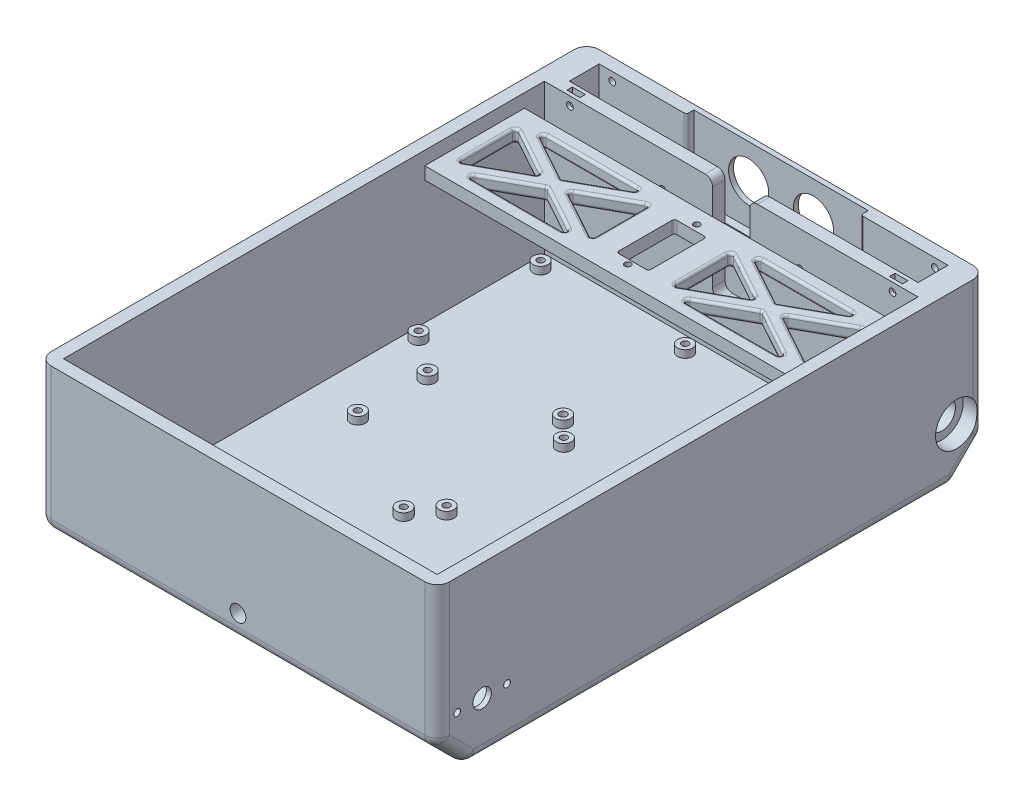
SolidWorks part; units mm, degrees
ref_plane "Front Plane" through (0, 0, 0) normal (0, 0, 1) x (1, 0, 0)
ref_plane "Top Plane" through (0, 0, 0) normal (0, 1, 0) x (1, 0, 0)
ref_plane "Right Plane" through (0, 0, 0) normal (1, 0, 0) x (0, 0, -1)
sketch "Main Body" plane through (0, 0, 0) normal (0, 1, 0) x (1, 0, 0)
  line L0 (-75, 110) -> (75, 110)
  line L1 (-75, -105) -> (75, -105)
  line L2 (-75, -105) -> (-75, 105)
  line L3 (-75, 105) -> (75, 105)
  line L4 (75, -105) -> (75, 105)
  line L5 (-75, -105) -> (75, 105) construction
  line L6 (-75, 105) -> (75, -105) construction
  line L7 (80, -105) -> (80, 105)
  line L8 (-75, -110) -> (75, -110)
  line L9 (-80, -105) -> (-80, 105)
  line L10 (-80, -110) -> (80, -110) construction
  line L11 (-80, -110) -> (-80, 110) construction
  line L12 (80, -110) -> (80, 110) construction
  line L13 (-80, 110) -> (80, 110) construction
  arc A0 (-75, -110) -> (-80, -105) centre (-75, -105) cw
  arc A1 (80, -105) -> (75, -110) centre (75, -105) cw
  arc A2 (75, 110) -> (80, 105) centre (75, 105) cw
  arc A3 (-75, 110) -> (-80, 105) centre (-75, 105) ccw
  point P0 (0, 0)
  dimension "D4" = 5
  dimension "D1" = 75
  dimension "D2" = 210
  dimension "D3" = 5
extrude "Boss-Extrude1" add sketch "Main Body" along normal blind 8 contours L1 L4 L3 L2 | L9 L8 L7 L0 L4 L1 L2 L3 region at (0, 0, -107.2797) region at (0, 0, 0)
extrude "Boss-Extrude3" add sketch "Main Body<4>" along normal blind 60 from surface starting at face at (0, 8, 0)
sketch "Main Body<4>" plane through (0, 0, 0) normal (0, 1, 0) x (1, 0, 0) same geometry as "Main Body"
sketch "Sketch1" plane through (75, 0, 0) normal (-1, 0, 0) x (0, 0, 1)
  line L0 (105, 68) -> (105, 8) construction
  line L1 (-105, 8) -> (105, 8) construction
  line L2 (79, 15.5) -> (105, 15.5)
  line L3 (79, 8) -> (105, 8)
  line L4 (79, 8) -> (79, 34)
  line L5 (79, 34) -> (105, 34)
  line L6 (105, 8) -> (105, 34)
  line L7 (79, 8) -> (105, 34) construction
  line L8 (79, 34) -> (105, 8) construction
  circle A0 centre (92, 21) radius 13
  line M2 (-105, 8) -> (105, 8)
  line M3 (105, 8) -> (105, 68)
  dimension "D1" = 26
  dimension "D2" = 7.5
extrude "Boss-Extrude4" add sketch "Sketch1" along normal up to surface (150 mm away) contours A0 L4 M2 | A0 L3 M3 region at (75, 10.5201, 82.0674) region at (75, 10.5201, 101.9326) up to face at (-75, 38, 0)
sketch "Sketch2" plane through (0, 0, 0) normal (1, 0, 0) x (0, 0, -1)
  line L0 (-105, 68) -> (-105, 15.5) construction
  line L1 (-105, 8) -> (-79, 8)
  line L2 (-105, 8) -> (-105, 15.5)
  line L3 (-105, 15.5) -> (-79, 15.5)
  line L4 (-79, 8) -> (-79, 15.5)
  line L5 (105, 8) -> (-79, 8) construction
  line L6 (-79, 8) -> (-79, 15.5) construction
  line L7 (-79, 15.5) -> (-80.2208, 15.5) construction
extrude "Cut-Extrude1" cut sketch "Sketch2" against normal mid plane 12
sketch "Sketch3" plane through (0, 8, 0) normal (0, 1, 0) x (1, 0, 0)
  line L0 (75, -105) -> (-75, -105) construction
  line L1 (-4, -79) -> (-11, -79)
  line L2 (-4, -79) -> (-4, -105)
  line L3 (-4, -105) -> (-11, -105)
  line L4 (-11, -79) -> (-11, -105)
  line L5 (0, 0) -> (0, -105) construction
  line L6 (-75, -79) -> (-6, -79) construction
  line L7 (11, -79) -> (11, -105)
  line L8 (4, -105) -> (11, -105)
  line L9 (4, -79) -> (4, -105)
  line L10 (4, -79) -> (11, -79)
  line L11 (-6, -103.7792) -> (-6, -92) construction
  dimension "D1" = 5
  dimension "D2" = 4
extrude "Boss-Extrude5" add sketch "Sketch3" along normal blind 20
sketch "Sketch4" plane through (0, 8, 0) normal (0, 1, 0) x (1, 0, 0)
  line L0 (-75, -105) -> (-75, 105) construction
  line L1 (-75, 93) -> (75, 93)
  line L2 (-75, 93) -> (-75, 88)
  line L3 (-75, 88) -> (75, 88)
  line L4 (75, 93) -> (75, 88)
  line L5 (75, 105) -> (75, -105) construction
  line L6 (-75, 105) -> (75, 105) construction
  dimension "D1" = 17
  dimension "D2" = 5
extrude "Boss-Extrude6" add sketch "Sketch4" along normal up to surface (60 mm away) up to face at (0, 68, 0)
sketch "Sketch5" plane through (80, 0, 0) normal (1, 0, 0) x (0, 0, -1)
  circle A0 centre (-92, 21) radius 3.5 construction
  circle A1 centre (-92, 21) radius 3.5
  circle A2 centre (-92, 21) radius 3.7
  dimension "D1" = 0.2
extrude "Cut-Extrude4" cut sketch "Sketch5" against normal up to next contours A1 | A2 A1 region at (80, 21, 92) region at (80, 21, 95.5953)
sketch "Sketch6" plane through (-75, 0, 0) normal (1, 0, 0) x (0, 0, -1)
  circle A0 centre (-92, 21) radius 13
  dimension "D1" = 26
extrude "Cut-Extrude5" cut sketch "Sketch6" against normal offset from surface (3 mm away) 2 up to face at (-80, 34, 0)
mirror "Mirror1" about plane through (0, 0, 0) normal (1, 0, 0) of "Cut-Extrude4"
sketch "Sketch8" plane through (75, 0, 0) normal (-1, 0, 0) x (0, 0, 1)
  circle A0 centre (92, 21) radius 13
  dimension "D1" = 26
extrude "Cut-Extrude6" cut sketch "Sketch8" against normal offset from surface (3 mm away) 2 up to face at (80, 21, 88.3)
sketch "Sketch10" plane through (80, 0, 0) normal (1, 0, 0) x (0, 0, -1)
  circle A1 centre (-82, 21) radius 1.25
  circle A2 centre (-82, 21) radius 1.25
  circle A3 centre (-102, 21) radius 1.25
  circle A4 centre (-102, 21) radius 1.25
  circle A5 centre (-92, 21) radius 12.5
  circle A6 centre (-92, 21) radius 12.5
  circle A63 centre (-102, 21) radius 1.35
  circle A64 centre (-82, 21) radius 1.35
  dimension "D4" = 2.7
extrude "Cut-Extrude7" cut sketch "Sketch10" against normal up to next contours A2 | A64 A2 | A4 | A63 A4 region at (80, 21, 82) region at (80, 21, 102) region at (80, 21, 103.3118) region at (80, 21, 83.3118)
mirror "Mirror3" about plane through (0, 0, 0) normal (1, 0, 0) of "Cut-Extrude7"
sketch "Sketch11" plane through (80, 0, 0) normal (1, 0, 0) x (0, 0, -1)
  circle A0 centre (98.55, 21.05) radius 4.45 construction
  circle A1 centre (98.55, 21.05) radius 4.45
  circle A3 centre (98.55, 21.05) radius 5.45
  dimension "D1" = 1
extrude "Cut-Extrude10" cut sketch "Sketch11" against normal through all contours A1 | A3 A1 region at (80, 21.05, -98.55) region at (80, 21.05, -93.2541)
sketch "Sketch12" plane through (-75, 0, 0) normal (1, 0, 0) x (0, 0, -1)
  line L0 (93, 8) -> (105, 8) construction
  line L1 (93, 68) -> (105, 68)
  line L2 (93, 68) -> (93, 8)
  line L3 (93, 8) -> (105, 8)
  line L4 (105, 68) -> (105, 8)
  line L6 (93, 68) -> (93, 8) construction
  line L7 (93, 68) -> (105, 68) construction
  circle A2 centre (98.55, 21.05) radius 5.45 construction
  circle A3 centre (98.55, 21.05) radius 5.45
extrude "Boss-Extrude7" add sketch "Sketch12" along normal blind 5
sketch "Sketch13" plane through (-80, 0, 0) normal (-1, 0, 0) x (0, 0, 1)
  circle A0 centre (-98.55, 21.05) radius 8.55
  circle A2 centre (-98.55, 21.05) radius 5.45 construction
  dimension "D1" = 17.1
extrude "Cut-Extrude11" cut sketch "Sketch13" against normal blind 6
mirror "Mirror4" about plane through (0, 0, 0) normal (1, 0, 0) of "Boss-Extrude7", "Cut-Extrude11"
sketch "Sketch14" plane through (0, 8, 0) normal (0, 1, 0) x (1, 0, 0)
  line L0 (-4, -105) -> (-4, -79) construction
  line L1 (-4, -95) -> (4, -95)
  line L2 (-4, -95) -> (-4, -105)
  line L3 (-4, -105) -> (4, -105)
  line L4 (4, -95) -> (4, -105)
  dimension "D1" = 10
extrude "Boss-Extrude9" add sketch "Sketch14" along normal blind 5
sketch "Sketch15" plane through (0, 0, 110) normal (0, 0, 1) x (1, 0, 0)
  arc A4 (3.15, 19.5) -> (-3.15, 19.5) centre (0, 19.5) ccw
  arc A5 (-3.15, 19.5) -> (3.15, 19.5) centre (0, 19.5) ccw
  arc A6 (3, 19.5) -> (-3, 19.5) centre (0, 19.5) ccw construction
  point P0 (3.8067, 18.2485)
  dimension "D1" = 3.15
extrude "Cut-Extrude12" cut sketch "Sketch15" against normal up to next contours A4 A5 region at (0, 19.5, 110)
sketch "Sketch16" plane through (0, 0, 0) normal (0, -1, 0) x (1, 0, 0)
  circle A0 centre (-12.5, -82) radius 1.475 construction
  circle A1 centre (-70.5, -82) radius 1.475 construction
  circle A2 centre (-70.5, -33) radius 1.475 construction
  circle A3 centre (-12.5, -33) radius 1.475 construction
  circle A4 centre (-4.2, -25) radius 1.475 construction
  circle A5 centre (-55, -21.12) radius 1.475 construction
  circle A6 centre (-55, 6.88) radius 1.475 construction
  circle A7 centre (-4.2, 22.08) radius 1.475 construction
  circle A8 centre (-12.3, 31.18) radius 1.475 construction
  circle A9 centre (24.2, 31.18) radius 1.475 construction
  circle A10 centre (37.8459, 24.117) radius 1.475 construction
  circle A11 centre (59.5541, 24.117) radius 1.475 construction
  circle A12 centre (59.5541, 68.243) radius 1.475 construction
  circle A13 centre (37.8459, 68.243) radius 1.475 construction
  circle A14 centre (24.2, 67.68) radius 1.475 construction
  circle A15 centre (-12.3, 67.68) radius 1.475 construction
  circle A16 centre (-12.5, -82) radius 1.475
  circle A17 centre (-70.5, -82) radius 1.475
  circle A18 centre (-70.5, -33) radius 1.475
  circle A19 centre (-12.5, -33) radius 1.475
  circle A20 centre (-4.2, -25) radius 1.475
  circle A21 centre (-55, -21.12) radius 1.475
  circle A22 centre (-55, 6.88) radius 1.475
  circle A23 centre (-4.2, 22.08) radius 1.475
  circle A24 centre (-12.3, 31.18) radius 1.475
  circle A25 centre (24.2, 31.18) radius 1.475
  circle A26 centre (37.8459, 24.117) radius 1.475
  circle A27 centre (59.5541, 24.117) radius 1.475
  circle A28 centre (59.5541, 68.243) radius 1.475
  circle A29 centre (37.8459, 68.243) radius 1.475
  circle A30 centre (24.2, 67.68) radius 1.475
  circle A31 centre (-12.3, 67.68) radius 1.475
  circle A32 centre (-70.5, -82) radius 1.35
  circle A33 centre (-12.5, -82) radius 1.35
  circle A34 centre (-12.5, -33) radius 1.35
  circle A35 centre (-4.2, -25) radius 1.35
  circle A36 centre (-55, -21.12) radius 1.35
  circle A37 centre (-70.5, -33) radius 1.35
  circle A38 centre (-55, 6.88) radius 1.35
  circle A39 centre (-12.3, 31.18) radius 1.35
  circle A40 centre (-4.2, 22.08) radius 1.35
  circle A41 centre (24.2, 31.18) radius 1.35
  circle A42 centre (37.8459, 24.117) radius 1.35
  circle A43 centre (59.5541, 24.117) radius 1.35
  circle A44 centre (37.8459, 68.243) radius 1.35
  circle A45 centre (59.5541, 68.243) radius 1.35
  circle A46 centre (24.2, 67.68) radius 1.35
  circle A47 centre (-12.3, 67.68) radius 1.35
  dimension "D1" = 2.7
extrude "Cut-Extrude13" cut sketch "Sketch16" against normal up to next contours A47 | A46 | A44 | A45 | A35 | A37 | A36 | A38 | A39 | A40 | A41 | A42 | A43 | A32 | A33 | A19 region at (-70.5, 0, -82) region at (-12.5, 0, -82) region at (-4.2, 0, -25) region at (-55, 0, -21.12) region at (-70.5, 0, -33) region at (-55, 0, 6.88) region at (-12.3, 0, 31.18) region at (-4.2, 0, 22.08) region at (24.2, 0, 31.18) region at (37.8459, 0, 24.117) region at (59.5541, 0, 24.117) region at (37.8459, 0, 68.243) region at (59.5541, 0, 68.243) region at (24.2, 0, 67.68) region at (-12.3, 0, 67.68)
sketch "Sketch18" plane through (75, 0, 0) normal (-1, 0, 0) x (0, 0, 1)
  line L1 (-80, 62.6) -> (-40, 62.6)
  line L2 (-80, 62.6) -> (-80, 57.6)
  line L3 (-80, 57.6) -> (-40, 57.6)
  line L4 (-40, 62.6) -> (-40, 57.6)
  line L5 (-88, 68) -> (105, 68) construction
  dimension "D1" = 5
  dimension "D2" = 30
  dimension "D3" = 40
  dimension "D4" = 5.4
extrude "Boss-Extrude11" add sketch "Sketch18" along normal up to next
sketch "Sketch19" plane through (0, 68, 0) normal (0, 1, 0) x (1, 0, 0)
  line L1 (-6.425, 71.625) -> (6.425, 71.625)
  line L2 (-6.425, 71.625) -> (-6.425, 48.375)
  line L3 (-6.425, 48.375) -> (6.425, 48.375)
  line L4 (6.425, 71.625) -> (6.425, 48.375)
  line L12 (-75, 80) -> (-75, 40)
  line L13 (-75, 40) -> (75, 40)
  line L14 (75, 40) -> (75, 80)
  line L15 (75, 80) -> (-75, 80)
  line L16 (-75, 80) -> (-75, 40)
  line L17 (-75, 40) -> (75, 40)
  line L18 (75, 40) -> (75, 80)
  line L19 (75, 80) -> (-75, 80)
  point P4 (0, 71.625)
  point P8 (0, 80)
  point P12 (6.425, 60)
  point P13 (75, 60)
  dimension "D1" = 23.25
  dimension "D2" = 12.85
  dimension "D3" = 0
extrude "Cut-Extrude14" cut sketch "Sketch19" against normal up to next contours L4 L1 L2 L3 region at (0, 68, -60)
sketch "Sketch21" plane through (0, 0, -110) normal (0, 0, -1) x (-1, 0, 0)
  circle A1 centre (-64.75, 64.5) radius 1.3
  circle A2 centre (-64.75, 64.5) radius 1.3
  circle A3 centre (64.75, 64.5) radius 1.3
  circle A4 centre (64.75, 64.5) radius 1.3
  circle A44 centre (-64.75, 64.5) radius 1.35
  circle A45 centre (64.75, 64.5) radius 1.35
  dimension "D3" = 2.7
extrude "Cut-Extrude16" cut sketch "Sketch21" against normal up to surface (22 mm away) contours A44 A2 | A2 | A45 A4 | A4 region at (64.75, 64.5, -110) region at (-64.75, 64.5, -110) region at (66.0618, 64.5, -110) region at (-63.4382, 64.5, -110) up to face at (0, 38, -88)
ref_plane "Plane1" through (0, 0, -90.5) normal (0, 0, -1) x (-1, 0, 0)
sketch "Sketch22" plane through (0, 0, -90.5) normal (0, 0, -1) x (-1, 0, 0)
  line L0 (-67.35, 66.0011) -> (-67.35, 68)
  line L1 (-62.15, 66.0011) -> (-64.75, 67.5022)
  line L2 (-64.75, 67.5022) -> (-67.35, 66.0011)
  line L3 (-67.35, 66.0011) -> (-67.35, 62.9989)
  line L4 (-67.35, 62.9989) -> (-64.75, 61.4978)
  line L5 (-64.75, 61.4978) -> (-62.15, 62.9989)
  line L6 (-62.15, 62.9989) -> (-62.15, 66.0011)
  line L7 (-67.35, 68) -> (-62.15, 68)
  line L8 (-62.15, 68) -> (-62.15, 66.0011)
  line L9 (70, 68) -> (-70, 68) construction
  line L10 (0, 0) -> (0, 68) construction
  line L11 (75, 68) -> (-75, 68) construction
  line L12 (64.75, 61.4978) -> (62.15, 62.9989)
  line L13 (67.35, 62.9989) -> (64.75, 61.4978)
  line L14 (64.75, 67.5022) -> (67.35, 66.0011)
  line L15 (67.35, 66.0011) -> (67.35, 62.9989)
  line L16 (67.35, 66.0011) -> (67.35, 68)
  line L17 (62.15, 62.9989) -> (62.15, 66.0011)
  line L18 (62.15, 68) -> (62.15, 66.0011)
  line L19 (67.35, 68) -> (62.15, 68)
  line L20 (62.15, 66.0011) -> (64.75, 67.5022)
  circle A0 centre (-64.75, 64.5) radius 2.6 construction
  circle A1 centre (-64.75, 64.5) radius 1.35 construction
  dimension "D1" = 5.2
extrude "Cut-Extrude17" cut sketch "Sketch22" against normal mid plane 2.2 contours L20 L17 L12 L13 L15 L14 | L18 L20 L14 L16 L19 | L5 L6 L1 L2 L3 L4 | L8 L7 L0 L2 L1 region at (67.2943, 67.0006, -90.5) region at (64.75, 64.5, -90.5) region at (-64.75, 64.5, -90.5) region at (-62.2057, 67.0006, -90.5)
sketch "Sketch23" plane through (0, 0, -110) normal (0, 0, -1) x (-1, 0, 0)
  circle A0 centre (64.75, 64.5) radius 2.5
  circle A1 centre (-64.75, 64.5) radius 2.5
  circle A2 centre (64.75, 64.5) radius 1.35 construction
  circle A3 centre (-64.75, 64.5) radius 1.35 construction
  dimension "D1" = 5
  dimension "D2" = 5
extrude "Cut-Extrude18" cut sketch "Sketch23" against normal mid plane 2.5
sketch "Sketch24" plane through (0, 62.6, 0) normal (0, 1, 0) x (1, 0, 0)
  circle A0 centre (0, 46.475) radius 1.2502
  arc A1 (0.4, 45.5583) -> (-0.4, 45.5583) centre (0, 46.475) ccw construction
  circle A2 centre (0, 74.175) radius 1.2502
  arc A3 (-0.4, 75.0917) -> (0, 73.1748) centre (0, 74.175) ccw construction
  point P5 (0.4, 45.5583)
  dimension "D1" = 0.25
extrude "Cut-Extrude19" cut sketch "Sketch24" against normal up to next
sketch "Sketch25" plane through (0, 62.6, 0) normal (0, 1, 0) x (1, 0, 0)
  line L1 (-11.3, 80) -> (11.3, 80)
  line L2 (-11.3, 80) -> (-11.3, 40)
  line L3 (-11.3, 40) -> (11.3, 40)
  line L4 (-75, 80) -> (-75, 40)
  line L5 (-75, 40) -> (75, 40)
  line L6 (75, 40) -> (75, 80)
  line L7 (75, 80) -> (-75, 80)
  line L8 (-75, 80) -> (-75, 40)
  line L9 (-75, 40) -> (75, 40)
  line L10 (75, 40) -> (75, 80)
  line L11 (75, 80) -> (-75, 80)
  line L12 (11.3, 80) -> (11.3, 40)
  line L13 (-11.3, 80) -> (11.3, 40) construction
  line L14 (-11.3, 40) -> (11.3, 80) construction
  line L15 (0, 80) -> (0, 40) construction
  line L16 (70, 75) -> (70, 45)
  line L17 (-70, 75) -> (-16.3, 75)
  line L18 (-70, 75) -> (-70, 45)
  line L19 (-70, 45) -> (-16.3, 45)
  line L20 (-16.3, 75) -> (-16.3, 45)
  line L21 (-70, 75) -> (-16.3, 45) construction
  line L22 (-70, 45) -> (-16.3, 75) construction
  line L23 (70, 75) -> (16.3, 45) construction
  line L24 (70, 45) -> (16.3, 75) construction
  line L25 (70, 75) -> (16.3, 75)
  line L26 (16.3, 75) -> (16.3, 45)
  line L27 (70, 45) -> (16.3, 45)
  line L28 (-75, 60) -> (-11.3, 60) construction
  line L29 (75, 60) -> (11.3, 60) construction
  line L30 (-70, 71.9362) -> (-48.3314, 60)
  line L31 (-16.3, 71.9362) -> (-37.9686, 60)
  line L32 (70, 71.9362) -> (48.3314, 60)
  line L33 (-48.3314, 60) -> (-70, 48.0638)
  line L34 (48.3314, 60) -> (70, 48.0638)
  line L35 (-65.199, 45) -> (-43.15, 57.1458)
  line L36 (65.199, 45) -> (43.15, 57.1458)
  line L37 (-43.15, 57.1458) -> (-21.101, 45)
  line L38 (43.15, 57.1458) -> (21.101, 45)
  line L39 (16.3, 71.9362) -> (37.9686, 60)
  line L40 (-37.9686, 60) -> (-16.3, 48.0638)
  line L41 (37.9686, 60) -> (16.3, 48.0638)
  line L42 (-65.199, 75) -> (-43.15, 62.8542)
  line L43 (65.199, 75) -> (43.15, 62.8542)
  line L44 (-43.15, 62.8542) -> (-21.101, 75)
  line L45 (43.15, 62.8542) -> (21.101, 75)
  line L46 (-75, 40) -> (-75, 80) construction
  line L47 (-75, 40) -> (75, 40) construction
  point P2 (0, 60)
  point P9 (-43.15, 60)
  point P10 (75, 60)
  point P24 (43.15, 60)
  point P62 (-54.1745, 68.9271)
  dimension "D2" = 150
  dimension "D3" = 5
  dimension "D4" = 5
  dimension "D5" = 5
  dimension "D6" = 26.6686
  dimension "D7" = 96.101
  dimension "D1" = 0
extrude "Cut-Extrude21" cut sketch "Sketch25" against normal up to next contours L37 L35 L19 | L33 L30 L18 | L42 L44 L17 | L31 L40 L20 | L41 L39 L26 | L45 L43 L25 | L36 L38 L27 | L32 L34 L16 region at (62.7771, 62.6, -60) region at (43.15, 62.6, -70.9514) region at (43.15, 62.6, -49.0486) region at (23.5229, 62.6, -60) region at (-43.15, 62.6, -70.9514) region at (-62.7771, 62.6, -60) region at (-23.5229, 62.6, -60) region at (-43.15, 62.6, -49.0486)
sketch "Sketch26" plane through (-80, 0, 0) normal (-1, 0, 0) x (0, 0, 1)
  line L0 (-110, 12.58) -> (-97.42, 0)
  line L1 (-110, 68) -> (-110, 0) construction
  line L2 (105, 0) -> (-105, 0) construction
  line L3 (-97.42, 0) -> (-92.42, 0)
  line L4 (-92.42, 0) -> (-110, 17.58)
  line L5 (-110, 17.58) -> (-110, 12.58)
  line L6 (-110, 12.58) -> (-110, 0)
  line L7 (-110, 0) -> (-97.42, 0)
  circle A1 centre (-98.55, 21.05) radius 8.55 construction
  line M5 (-105, 15.4375) -> (-105, 0)
  line M6 (-105, 0) -> (105, 0)
  dimension "D1" = 2
  dimension "D2" = 5
  dimension "D3" = 45
extrude "Cut-Extrude22" cut sketch "Sketch26" against normal up to next contours L6 L7 L0 M5 | L0 M5 M6 region at (-80, 5.1434, -107.7067) region at (-80, 2.5267, -102.4733)
mirror "Mirror5" about plane through (0, 0, 0) normal (0, 0, 1) of "Cut-Extrude22"
fillet "Fillet1" radius 5 14 edges at (80, 3.79, -101.21) (78.5355, 11.1156, -108.5355) (-80, 3.79, -101.21) (-78.5355, 11.1156, -108.5355) (80, 3.79, 101.21) (78.5355, 11.1156, 108.5355) (-80, 3.79, 101.21) (-78.5355, 11.1156, 108.5355) (0, 0, -97.42) (0, 12.58, -110) (0, 0, 97.42) (0, 12.58, 110) (-80, 0, 0) (80, 0, 0)
fillet "Fillet2" radius 1 76 edges at (-32.1255, 57.6, -51.0729) (-32.1255, 62.6, -51.0729) (-21.101, 60.1, -45) (-43.15, 62.6, -45) (-43.15, 57.6, -45) (-54.1745, 57.6, -51.0729) (-65.199, 60.1, -45) (-54.1745, 62.6, -51.0729) (-43.15, 60.1, -57.1458) (32.1255, 57.6, -68.9271) (32.1255, 62.6, -68.9271) (21.101, 60.1, -75) (43.15, 62.6, -75) (43.15, 57.6, -75) (54.1745, 57.6, -68.9271) (65.199, 60.1, -75) (54.1745, 62.6, -68.9271) (43.15, 60.1, -62.8542) (54.1745, 62.6, -51.0729) (54.1745, 57.6, -51.0729) (43.15, 57.6, -45) (65.199, 60.1, -45) (43.15, 62.6, -45) (21.101, 60.1, -45) (32.1255, 62.6, -51.0729) (43.15, 60.1, -57.1458) (32.1255, 57.6, -51.0729) (59.1657, 62.6, -65.9681) (59.1657, 57.6, -65.9681) (70, 57.6, -60) (70, 60.1, -71.9362) (70, 62.6, -60) (70, 60.1, -48.0638) (59.1657, 62.6, -54.0319) (48.3314, 60.1, -60) (59.1657, 57.6, -54.0319) (-54.1745, 62.6, -68.9271) (-54.1745, 57.6, -68.9271) (-43.15, 57.6, -75) (-65.199, 60.1, -75) (-43.15, 62.6, -75) (-21.101, 60.1, -75) (-32.1255, 62.6, -68.9271) (-43.15, 60.1, -62.8542) (-32.1255, 57.6, -68.9271) (-59.1657, 57.6, -54.0319) (-59.1657, 62.6, -54.0319) (-70, 60.1, -48.0638) (-70, 62.6, -60) (-70, 57.6, -60) (-59.1657, 57.6, -65.9681) (-70, 60.1, -71.9362) (-59.1657, 62.6, -65.9681) (-48.3314, 60.1, -60) (-27.1343, 62.6, -65.9681) (-27.1343, 57.6, -65.9681) (-16.3, 57.6, -60) (-16.3, 60.1, -71.9362) (-16.3, 62.6, -60) (-16.3, 60.1, -48.0638) (-27.1343, 62.6, -54.0319) (-37.9686, 60.1, -60) (-27.1343, 57.6, -54.0319) (27.1343, 57.6, -54.0319) (27.1343, 62.6, -54.0319) (16.3, 60.1, -48.0638) (16.3, 62.6, -60) (16.3, 57.6, -60) (27.1343, 57.6, -65.9681) (16.3, 60.1, -71.9362) (27.1343, 62.6, -65.9681) (37.9686, 60.1, -60) (6.425, 60.1, -48.375) (-6.425, 60.1, -48.375) (-6.425, 60.1, -71.625) (6.425, 60.1, -71.625)
sketch "Sketch33" plane through (0, 0, -110) normal (0, 0, -1) x (-1, 0, 0)
  circle A0 centre (-13, 53.9999) radius 8.075
  circle A1 centre (13, 53.9999) radius 8.075
  circle A2 centre (-13, 53.9999) radius 7.3 construction
  circle A3 centre (13, 53.9999) radius 7.3 construction
  dimension "D1" = 16.15
extrude "Cut-Extrude27" cut sketch "Sketch33" against normal up to next
sketch "Sketch34" plane through (0, 0, -93) normal (0, 0, -1) x (-1, 0, 0)
  circle A0 centre (27.525, 54) radius 1.35 construction
  circle A1 centre (27.525, 54) radius 1.35
  circle A2 centre (-27.525, 54) radius 1.35 construction
  circle A3 centre (-27.525, 54) radius 1.35
  circle A4 centre (-27.525, 54) radius 1.35
  circle A5 centre (27.525, 54) radius 1.35
  dimension "D1" = 2.7
  dimension "D2" = 2.7
extrude "Cut-Extrude28" cut sketch "Sketch34" against normal up to next contours A3 | A1 region at (-27.525, 54, -93) region at (27.525, 54, -93)
sketch "Sketch35" plane through (0, 68, 0) normal (0, 1, 0) x (1, 0, 0)
  line L0 (70, 93) -> (-70, 93) construction
  line L1 (-7.5, 93) -> (7.5, 93)
  line L2 (-7.5, 93) -> (-7.5, 88)
  line L3 (-7.5, 88) -> (7.5, 88)
  line L4 (7.5, 93) -> (7.5, 88)
  line L5 (-7.5, 93) -> (7.5, 88) construction
  line L6 (-7.5, 88) -> (7.5, 93) construction
  line L7 (-75, 88) -> (75, 88) construction
  point P0 (0, 90.5)
  dimension "D1" = 15
extrude "Cut-Extrude29" cut sketch "Sketch35" against normal offset from surface (41 mm away) 19 up to face at (-4.2, 8, -23.65)
fillet "Fillet4" radius 3 9 edges at (0, 8, 95) (-7.5, 28, 79) (-7.5, 28, 105) (7.5, 28, 105) (7.5, 28, 79) (-7.5, 68, -90.5) (7.5, 68, -90.5) (-7.5, 27, -90.5) (7.5, 27, -90.5)
fillet "Fillet5" radius 1 1 edges at (0, 13, 95)
sketch "Sketch36" plane through (0, 68, 0) normal (0, 1, 0) x (1, 0, 0)
  line L0 (-70, 105) -> (70, 105) construction
  line L1 (-35, 108) -> (35, 108)
  line L2 (-35, 108) -> (-35, 105)
  line L3 (-35, 105) -> (35, 105)
  line L4 (35, 108) -> (35, 105)
  line L5 (-75, 110) -> (75, 110) construction
  point P6 (0, 108)
  dimension "D1" = 70
  dimension "D2" = 2
extrude "Cut-Extrude30" cut sketch "Sketch36" against normal blind 30
fillet "Fillet6" radius 1 2 edges at (35, 53, -105) (-35, 53, -105)
sketch "Sketch37" plane through (0, 8, 0) normal (0, 1, 0) x (1, 0, 0)
  line L8 (-4, -79) -> (-4, -92)
  line L9 (-4, -92) -> (4, -92)
  line L10 (4, -92) -> (4, -79)
  line L11 (4, -79) -> (75, -79)
  line L12 (75, -79) -> (75, 88)
  line L13 (75, 88) -> (-75, 88)
  line L14 (-75, 88) -> (-75, -79)
  line L15 (-75, -79) -> (-4, -79)
  line L16 (-4, -79) -> (-4, -92)
  line L17 (-4, -92) -> (4, -92)
  line L18 (4, -92) -> (4, -79)
  line L19 (4, -79) -> (75, -79)
  line L20 (75, -79) -> (75, 88)
  line L21 (75, 88) -> (-75, 88)
  line L22 (-75, 88) -> (-75, -79)
  line L23 (-75, -79) -> (-4, -79)
  circle A0 centre (-12.5, 82) radius 1.35 construction
  circle A1 centre (-4.2, 25) radius 1.35 construction
  circle A2 centre (-12.5, 33) radius 1.475 construction
  circle A3 centre (-70.5, 33) radius 1.35 construction
  circle A4 centre (-55, 21.12) radius 1.35 construction
  circle A5 centre (-55, -6.88) radius 1.35 construction
  circle A6 centre (-12.3, -31.18) radius 1.35 construction
  circle A7 centre (-4.2, -22.08) radius 1.35 construction
  circle A8 centre (24.2, -31.18) radius 1.35 construction
  circle A9 centre (37.8459, -24.117) radius 1.35 construction
  circle A10 centre (59.5541, -24.117) radius 1.35 construction
  circle A11 centre (59.5541, -68.243) radius 1.35 construction
  circle A12 centre (37.8459, -68.243) radius 1.35 construction
  circle A13 centre (24.2, -67.68) radius 1.35 construction
  circle A14 centre (-12.3, -67.68) radius 1.35 construction
  circle A15 centre (-70.5, 82) radius 1.35 construction
  circle A16 centre (-12.5, 82) radius 1.35
  circle A17 centre (-4.2, 25) radius 1.35
  circle A18 centre (-12.5, 33) radius 1.475
  circle A19 centre (-70.5, 33) radius 1.35
  circle A20 centre (-55, 21.12) radius 1.35
  circle A21 centre (-55, -6.88) radius 1.35
  circle A22 centre (-12.3, -31.18) radius 1.35
  circle A23 centre (-4.2, -22.08) radius 1.35
  circle A24 centre (24.2, -31.18) radius 1.35
  circle A25 centre (37.8459, -24.117) radius 1.35
  circle A26 centre (59.5541, -24.117) radius 1.35
  circle A27 centre (59.5541, -68.243) radius 1.35
  circle A28 centre (37.8459, -68.243) radius 1.35
  circle A29 centre (24.2, -67.68) radius 1.35
  circle A30 centre (-12.3, -67.68) radius 1.35
  circle A31 centre (-70.5, 82) radius 1.35
  circle A32 centre (-12.3, -67.68) radius 3
  circle A33 centre (24.2, -67.68) radius 3
  circle A34 centre (37.8459, -68.243) radius 3
  circle A35 centre (59.5541, -68.243) radius 3
  circle A36 centre (24.2, -31.18) radius 3
  circle A37 centre (37.8459, -24.117) radius 3
  circle A38 centre (59.5541, -24.117) radius 3
  circle A39 centre (-4.2, -22.08) radius 3
  circle A40 centre (-12.3, -31.18) radius 3
  circle A41 centre (-4.2, 25) radius 3
  circle A42 centre (-55, -6.88) radius 3
  circle A43 centre (-55, 21.12) radius 3
  circle A44 centre (-12.5, 33) radius 3
  circle A45 centre (-12.5, 82) radius 3
  circle A46 centre (-70.5, 82) radius 3
  circle A47 centre (-70.5, 33) radius 3
  circle M9 centre (-4.2, 25) radius 1.35
  circle M10 centre (59.5541, -68.243) radius 1.35
  circle M11 centre (37.8459, -68.243) radius 1.35
  circle M12 centre (24.2, -67.68) radius 1.35
  circle M13 centre (-70.5, 33) radius 1.35
  circle M14 centre (-55, 21.12) radius 1.35
  circle M15 centre (-55, -6.88) radius 1.35
  circle M16 centre (-12.3, -31.18) radius 1.35
  circle M17 centre (-4.2, -22.08) radius 1.35
  circle M18 centre (24.2, -31.18) radius 1.35
  circle M19 centre (37.8459, -24.117) radius 1.35
  circle M20 centre (59.5541, -24.117) radius 1.35
  circle M21 centre (-70.5, 82) radius 1.35
  circle M22 centre (-12.5, 82) radius 1.35
  circle M23 centre (-12.5, 33) radius 1.475
  circle M24 centre (-12.3, -67.68) radius 1.35
  dimension "D2" = 6
  dimension "D1" = 0
extrude "Boss-Extrude12" add sketch "Sketch37" along normal blind 3 contours A46 M21 | A45 M22 | A44 M23 | A41 M9 | A47 M13 | A43 M14 | A42 M15 | A38 M20 | A35 M10 | A34 M11 | A37 M19 | A36 M18 | A33 M12 | A39 M17 | A40 M16 | A32 M24 region at (-15.2151, 8, 67.68) region at (21.2849, 8, 67.68) region at (34.9307, 8, 68.243) region at (56.639, 8, 68.243) region at (21.2849, 8, 31.18) region at (34.9307, 8, 24.117) region at (56.639, 8, 24.117) region at (-7.1151, 8, 22.08) region at (-15.2151, 8, 31.18) region at (-7.1151, 8, -25) region at (-57.9151, 8, 6.88) region at (-57.9151, 8, -21.12) region at (-15.4151, 8, -33) region at (-15.4151, 8, -82) region at (-73.4151, 8, -82) region at (-73.4151, 8, -33)
equation "\"Screw\"= 2.7"
equation "\"D1@Sketch16\"=\"Screw\""
equation "\"D4@Sketch10\"=\"Screw\""
equation "\"D3@Sketch21\"=\"Screw\""
equation "\"D2@Sketch34\"=\"Screw\""
equation "\"D1@Sketch34\"=\"Screw\""
